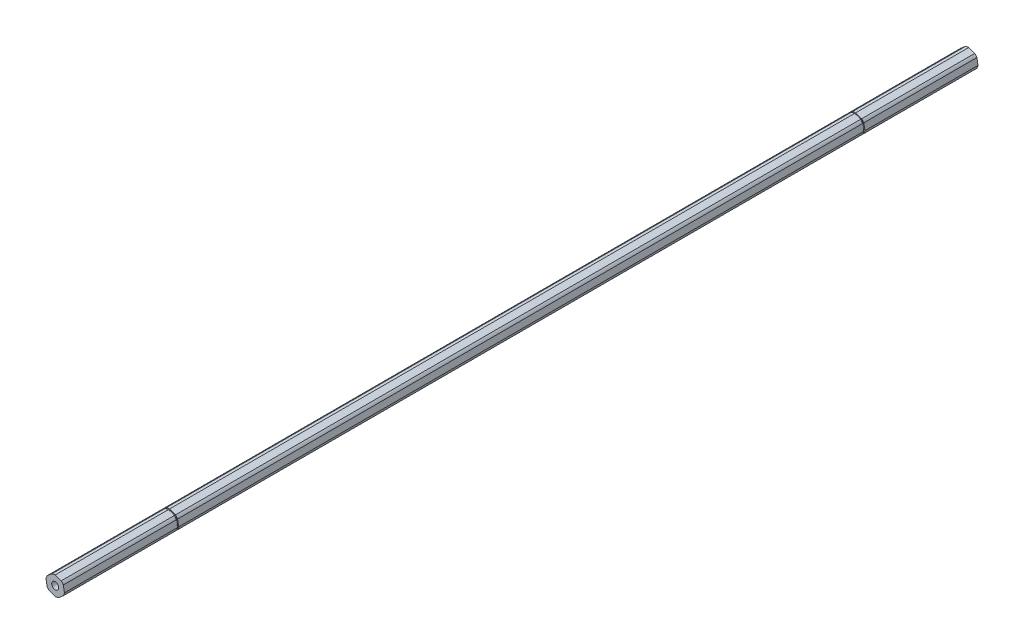
SolidWorks part; units mm, degrees
material "7075-T6 (SN)"
ref_plane "Front Plane" through (0, 0, 0) normal (0, 0, 1) x (1, 0, 0)
ref_plane "Top Plane" through (0, 0, 0) normal (0, 1, 0) x (1, 0, 0)
ref_plane "Right Plane" through (0, 0, 0) normal (1, 0, 0) x (0, 0, -1)
sketch "Sketch1" plane through (0, 0, 0) normal (0, 0, 1) x (1, 0, 0)
  line L1 (-6.6545, 1.1312) -> (-5.8457, -3.375)
  line L2 (-4.3069, -5.1974) -> (0, -6.75)
  line L3 (2.3476, -6.3286) -> (5.8457, -3.375)
  line L4 (6.6545, -1.1312) -> (5.8457, 3.375)
  line L5 (4.3069, 5.1974) -> (0, 6.75)
  line L6 (-2.3476, 6.3286) -> (-5.8457, 3.375)
  circle A0 centre (0, 0) radius 6.35 construction
  arc A1 (-5.8457, 3.375) -> (-6.6545, 1.1312) centre (0, 0) ccw
  arc A2 (-5.8457, -3.375) -> (-4.3069, -5.1974) centre (0, 0) ccw
  arc A3 (0, -6.75) -> (2.3476, -6.3286) centre (0, 0) ccw
  arc A4 (5.8457, -3.375) -> (6.6545, -1.1312) centre (0, 0) ccw
  arc A5 (5.8457, 3.375) -> (4.3069, 5.1974) centre (0, 0) ccw
  arc A6 (0, 6.75) -> (-2.3476, 6.3286) centre (0, 0) ccw
  dimension "D1" = 12.7
  dimension "D2" = 13.5
extrude "Boss-Extrude1" add sketch "Sketch1" along normal mid plane 660.4
sketch "Sketch2" plane through (0, 0, 330.2) normal (0, 0, 1) x (1, 0, 0)
  circle A0 centre (0, 0) radius 2.0193
  dimension "D1" = 4.0386
extrude "Cut-Extrude1" cut sketch "Sketch2" against normal through all
hole_wizard "1/4-20 Tapped Hole1" positions "Sketch5" profile "Sketch6" tap size "1/4-20" standard "ANSI Inch"
sketch "Sketch5" plane through (0, 0, 330.2) normal (0, 0, 1) x (1, 0, 0)
  point P0 (0, 0)
sketch "Sketch6" plane through (0, 0, 330.2) normal (1, 0, 0) x (0, -1, 0)
  line L0 (0, 0) -> (0, 20.5838)
  line L1 (0, 20.5838) -> (2.5527, 19.05)
  line L2 (2.5527, 19.05) -> (2.5527, 0)
  line L5 (2.5527, 0) -> (0, 0)
  line L10 (0, 20.5838) -> (-2.5527, 19.05) construction
  line L11 (0, -6.35) -> (0, 107.95) construction
  dimension "Tap Drill Dia." = 5.1054
  dimension "Tap Drill Depth" = 19.05
  dimension "Drill Angle" = 118
cosmetic thread "Hole Thread1" parameters "D1"=12.7, "D2"=6.35
hole_wizard "1/4-20 Tapped Hole2" positions "Sketch7" profile "Sketch8" tap size "1/4-20" standard "ANSI Inch"
sketch "Sketch7" plane through (0, 0, -330.2) normal (0, 0, -1) x (-1, 0, 0)
  point P0 (0, 0)
sketch "Sketch8" plane through (0, 0, -330.2) normal (1, 0, 0) x (0, 1, 0)
  line L0 (0, 0) -> (0, 20.5838)
  line L1 (0, 20.5838) -> (2.5527, 19.05)
  line L2 (2.5527, 19.05) -> (2.5527, 0)
  line L5 (2.5527, 0) -> (0, 0)
  line L10 (0, 20.5838) -> (-2.5527, 19.05) construction
  line L11 (0, -6.35) -> (0, 107.95) construction
  dimension "Tap Drill Dia." = 5.1054
  dimension "Tap Drill Depth" = 19.05
  dimension "Drill Angle" = 118
cosmetic thread "Hole Thread2" parameters "D1"=12.7, "D2"=6.35
sketch "Sketch11" plane through (0, 0, 0) normal (0, 1, 0) x (1, 0, 0)
  line L0 (0, 0) -> (0, -330.2) construction
sketch "Sketch10" plane through (0, 0.5654, 0) normal (1, 0, 0) x (0, 0, -1)
  line L0 (-330.2, 6.1846) -> (330.2, 6.1846) construction
  line L1 (247.5738, 6.1846) -> (248.4628, 6.1846)
  line L2 (247.5738, 6.1846) -> (247.5738, 5.3782)
  line L3 (247.5738, 5.3782) -> (248.4628, 5.3782)
  line L4 (248.4628, 6.1846) -> (248.4628, 5.3782)
  line L5 (247.5738, 6.1846) -> (248.4628, 5.3782) construction
  line L6 (247.5738, 5.3782) -> (248.4628, 6.1846) construction
  line L8 (330.2, 4.632) -> (330.2, 6.1846) construction
  point P4 (248.0183, 5.7814)
  dimension "D1" = 0.889
  dimension "D2" = 5.9436
  dimension "D3" = 81.7372
revolve "Cut-Revolve1" cut sketch "Sketch10" angle 360 about L0
mirror "Mirror1" about plane through (0, 0, 0) normal (0, 0, 1) of "Cut-Revolve1"
